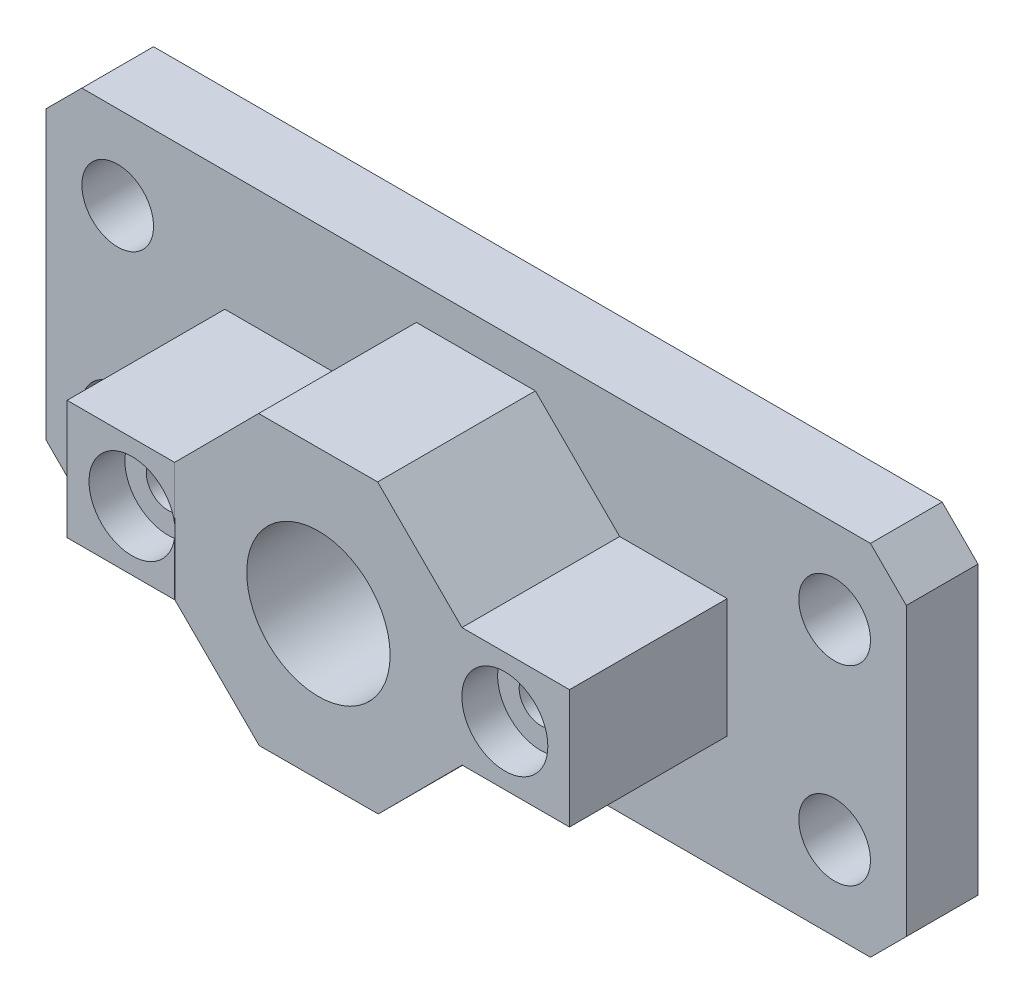
SolidWorks part; units mm, degrees
ref_plane "Спереди" through (0, 0, 0) normal (0, 0, 1) x (1, 0, 0)
ref_plane "Сверху" through (0, 0, 0) normal (0, 1, 0) x (1, 0, 0)
ref_plane "Справа" through (0, 0, 0) normal (1, 0, 0) x (0, 0, -1)
sketch "Эскиз1" plane through (0, 0, 0) normal (0, 0, 1) x (1, 0, 0)
  line L0 (-60, 0) -> (60, 0) construction
  line L1 (-60, 25) -> (60, 25)
  line L2 (-60, 25) -> (-60, -25)
  line L3 (-60, -25) -> (60, -25)
  line L4 (60, 25) -> (60, -25)
  line L5 (-60, 25) -> (60, -25) construction
  line L6 (-60, -25) -> (60, 25) construction
  line L7 (0, 25) -> (0, -25)
  line L8 (-60, 13.3) -> (-50, 13.3)
  line L9 (20.0553, -8.2581) -> (20.0206, 8.3419)
  line L10 (20.0206, 8.3419) -> (8.2581, 20.0553)
  line L11 (8.2581, 20.0553) -> (-8.3419, 20.0206)
  line L12 (-8.3419, 20.0206) -> (-20.0553, 8.2581)
  line L13 (-20.0553, 8.2581) -> (-20.0206, -8.3419)
  line L14 (-20.0206, -8.3419) -> (-8.2581, -20.0553)
  line L15 (-8.2581, -20.0553) -> (8.3419, -20.0206)
  line L16 (8.3419, -20.0206) -> (20.0553, -8.2581)
  line L17 (-50, 13.3) -> (-50, 0)
  line L18 (-60, 13.3) -> (60, 13.3)
  line L19 (-26, 0) -> (-26, -33.6007)
  line L20 (-20.0553, 8.2581) -> (-35.0553, 8.2581)
  line L21 (-20.0553, 8.2581) -> (-20.0553, -8.3419)
  line L22 (-20.0553, -8.3419) -> (-35.0553, -8.3419)
  line L23 (-35.0553, 8.2581) -> (-35.0553, -8.3419)
  line L24 (20.0206, 8.3419) -> (35.0206, 8.3419)
  line L25 (20.0206, 8.3419) -> (20.0206, -8.2581)
  line L26 (20.0206, -8.2581) -> (35.0206, -8.2581)
  line L27 (35.0206, 8.3419) -> (35.0206, -8.2581)
  line L28 (-26, -33.6007) -> (0, -33.6007)
  line L29 (0, -33.6007) -> (0, 0)
  circle A0 centre (0, 0) radius 20.038 construction
  circle A1 centre (-50, 13.3) radius 5
  circle A2 centre (-50, -13.3) radius 5
  circle A3 centre (50, -13.3) radius 5
  circle A4 centre (50, 13.3) radius 5
  circle A5 centre (0, 0) radius 10
  point P0 (0, 0)
  point P37 (26, 0)
  dimension "D6" = 10
  dimension "D9" = 20
  dimension "D1" = 50
  dimension "D2" = 120
  dimension "D3" = 16.6
  dimension "D4" = 10
  dimension "D5" = 13.3
  dimension "D7" = 15
  dimension "D8" = 15
  dimension "D10" = 26
extrude "Бобышка-Вытянуть1" add sketch "Эскиз1" along normal blind 10 contours L2 L3 L4 L1
extrude "Вырез-Вытянуть1" cut sketch "Эскиз1<4>" against normal through all from surface contours A1 starting at face at (0, 0, 10)
sketch "Эскиз1<4>" plane through (0, 0, 0) normal (0, 0, 1) x (1, 0, 0) same geometry as "Эскиз1"
extrude "Вырез-Вытянуть2" cut sketch "Эскиз1<5>" against normal through all from surface contours A2 starting at face at (-55, 13.3, 10)
sketch "Эскиз1<5>" plane through (0, 0, 0) normal (0, 0, 1) x (1, 0, 0) same geometry as "Эскиз1"
extrude "Вырез-Вытянуть3" cut sketch "Эскиз1<6>" against normal through all from surface contours A4 starting at face at (-55, -13.3, 10)
sketch "Эскиз1<6>" plane through (0, 0, 0) normal (0, 0, 1) x (1, 0, 0) same geometry as "Эскиз1"
extrude "Вырез-Вытянуть4" cut sketch "Эскиз1<7>" against normal through all from surface contours A3 starting at face at (45, 13.3, 10)
sketch "Эскиз1<7>" plane through (0, 0, 0) normal (0, 0, 1) x (1, 0, 0) same geometry as "Эскиз1"
extrude "Бобышка-Вытянуть2" add sketch "Эскиз1<8>" along normal blind 22 from surface contours L9 L10 L11 L12 L13 L14 L15 L16 starting at face at (45, -13.3, 10)
sketch "Эскиз1<8>" plane through (0, 0, 0) normal (0, 0, 1) x (1, 0, 0) same geometry as "Эскиз1"
extrude "Бобышка-Вытянуть7" add sketch "Эскиз1<9>" along normal blind 22 from surface separate body contours L20 L23 L22 L21 starting at face at (0, 0, 10)
sketch "Эскиз1<9>" plane through (0, 0, 0) normal (0, 0, 1) x (1, 0, 0) same geometry as "Эскиз1"
extrude "Бобышка-Вытянуть8" add sketch "Эскиз1<10>" along normal blind 22 from surface contours L24 L27 L26 L25 starting at face at (0, 0, 10)
sketch "Эскиз1<10>" plane through (0, 0, 0) normal (0, 0, 1) x (1, 0, 0) same geometry as "Эскиз1"
extrude "Вырез-Вытянуть5" cut sketch "Эскиз1<11>" against normal blind 22 from surface contours A5 starting at face at (7.0041, 0.0084, 32)
sketch "Эскиз1<11>" plane through (0, 0, 0) normal (0, 0, 1) x (1, 0, 0) same geometry as "Эскиз1"
hole_wizard "Цековка для  болта с шестигранной головкой M52" positions "Эскиз10" profile "Эскиз11" counterbore size "M5" standard "ISO"
sketch "Эскиз10" plane through (0, 0, 32) normal (0, 0, 1) x (1, 0, 0)
  point P0 (-26, 0)
  point P3 (26, 0)
sketch "Эскиз11" plane through (-26, 0, 32) normal (1, 0, 0) x (0, -1, 0)
  line L0 (0, 0) -> (0, 25)
  line L1 (0, 25) -> (3, 25)
  line L2 (3, 25) -> (3, 5)
  line L3 (3, 5) -> (6, 5)
  line L4 (6, 5) -> (6, 0)
  line L5 (6, 0) -> (0, 0)
  line L10 (0, 25) -> (-3, 25) construction
  line L11 (0, -6.35) -> (0, 107.95) construction
  dimension "Диаметр отверстия" = 6
  dimension "Глубина отверстия" = 25
  dimension "Диаметр цековки" = 12
  dimension "Глубина цековки" = 5
  dimension "Угол заточки сверла" = 180
chamfer "Фаска4" distance 5 angle 45 4 edges at (-60, -25, 5) (-60, 25, 5) (60, 25, 5) (60, -25, 5)
